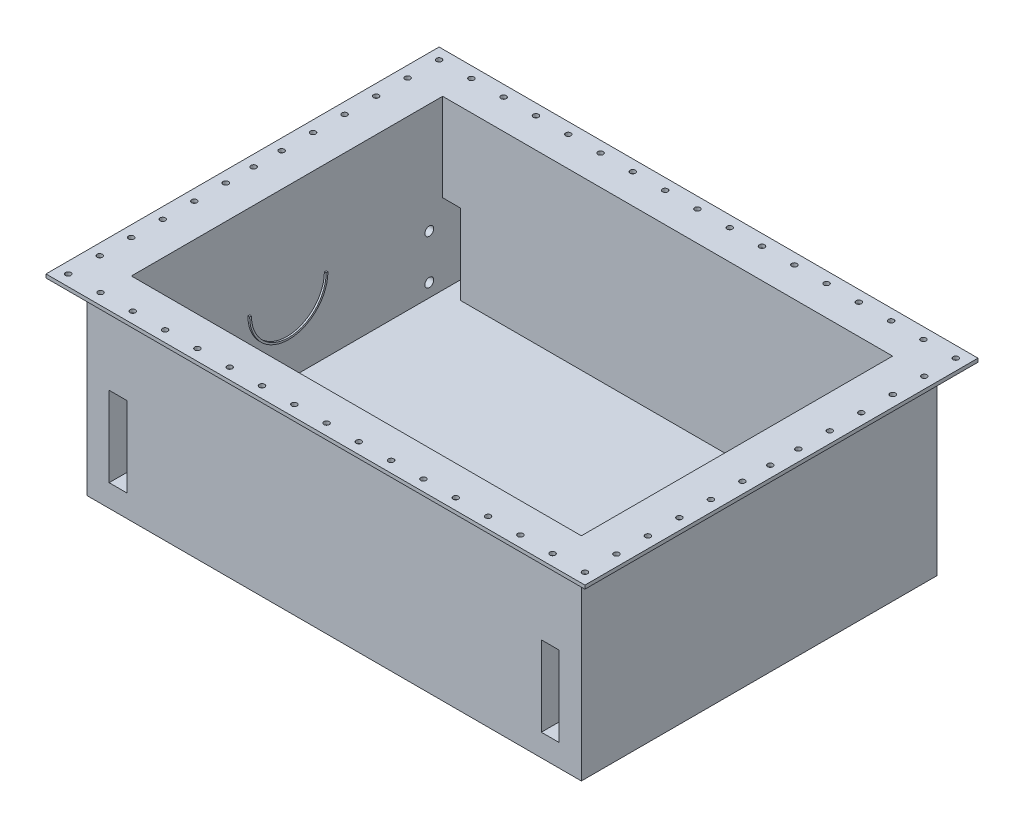
SolidWorks part; units mm, degrees
material "2195 Aluminum"
ref_plane "Front Plane" through (0, 0, 0) normal (0, 0, 1) x (1, 0, 0)
ref_plane "Top Plane" through (0, 0, 0) normal (0, 1, 0) x (1, 0, 0)
ref_plane "Right Plane" through (0, 0, 0) normal (1, 0, 0) x (0, 0, -1)
sketch "Sketch2" plane through (0, 0, 0) normal (0, 1, 0) x (1, 0, 0)
  line L0 (0, 437.5) -> (0, -437.5) construction
  line L1 (-632.5, 437.5) -> (632.5, 437.5)
  line L2 (-632.5, 437.5) -> (-632.5, -437.5)
  line L3 (-632.5, -437.5) -> (632.5, -437.5)
  line L4 (632.5, 437.5) -> (632.5, -437.5)
  line L5 (-632.5, 0) -> (632.5, 0) construction
  line L6 (-695, 48.7342) -> (-632.5, 48.7342) construction
  line L7 (-695, 500) -> (695, 500)
  line L8 (-695, 500) -> (-695, -500)
  line L9 (-695, -500) -> (695, -500)
  line L10 (695, 500) -> (695, -500)
  line L11 (632.5, 75.1796) -> (695, 75.1796) construction
  line L12 (-4.9015, 500) -> (-4.9015, 437.5) construction
  line L13 (-4.9015, -437.5) -> (-4.9015, -500) construction
  dimension "D1" = 62.5
  dimension "D2" = 1000
  dimension "D3" = 1390
extrude "Boss-Extrude1" add sketch "Sketch2" against normal blind 534.5
sketch "Sketch3" plane through (0, -534.5, 0) normal (0, -1, 0) x (1, 0, 0)
  line L0 (-695, 500) -> (-695, -500)
  line L3 (-695, 500) -> (695, 500)
  line L4 (695, -500) -> (695, 500)
  line L5 (-695, -500) -> (695, -500)
  line L6 (695, 500) -> (695, -500) construction
  line L7 (-695, 500) -> (695, 500) construction
  line L8 (-695, -500) -> (-695, 500) construction
  line L9 (695, -500) -> (-695, -500) construction
extrude "Boss-Extrude2" add sketch "Sketch3" against normal blind 62.5
sketch "Sketch4" plane through (695, 0, 0) normal (1, 0, 0) x (0, 0, -1)
  line L1 (0, 0) -> (0, -580.2055) construction
  line L2 (-105, -261) -> (-110, -261)
  line L3 (105, -261) -> (110, -261)
  arc A0 (-105, -261) -> (105, -261) centre (0, -261) ccw
  arc A1 (-110, -261) -> (110, -261) centre (0, -261) ccw
  dimension "D2" = 210
  dimension "D3" = 220
  dimension "D1" = 261
extrude "MMRTG Holder" add sketch "Sketch4" against normal blind 5 from offset 62.5 offset against normal yes
mirror "Mirror1" about plane through (0, 0, 0) normal (1, 0, 0) of "MMRTG Holder"
sketch "Sketch5" plane through (695, 0, 0) normal (1, 0, 0) x (0, 0, -1)
  line L0 (0, 70.8163) -> (0, -598.8061) construction
  line L1 (-500, -534.5) -> (500, -534.5) construction
  line L2 (-500, -534.5) -> (-500, 0) construction
  line L3 (-400, 39.1953) -> (-400, -618.3368) construction
  circle A0 centre (-400, -309.5) radius 12.5
  circle A1 centre (-400, -434.5) radius 12.5
  circle A2 centre (400, -434.5) radius 12.5
  circle A3 centre (400, -309.5) radius 12.5
  dimension "D4" = 25
  dimension "D1" = 125
  dimension "D2" = 100
  dimension "D3" = 100
extrude "Suspension Bolt Holes" cut sketch "Sketch5" against normal through all
sketch "Sketch6" plane through (0, 0, -500) normal (0, 0, -1) x (-1, 0, 0)
  line L0 (-695, -534.5) -> (-695, 0) construction
  line L1 (-632.5, -472) -> (-582.5, -472)
  line L2 (-632.5, -472) -> (-632.5, -247)
  line L3 (-632.5, -247) -> (-582.5, -247)
  line L4 (-582.5, -472) -> (-582.5, -247)
  line L5 (-695, -534.5) -> (695, -534.5) construction
  dimension "D1" = 62.5
  dimension "D2" = 62.5
  dimension "D3" = 50
  dimension "D4" = 225
extrude "Control Arm Cutout" cut sketch "Sketch6" against normal up to next
mirror "Mirror2" about plane through (0, 0, 0) normal (1, 0, 0) of "Control Arm Cutout"
mirror "Mirror3" about plane through (0, 0, 0) normal (0, 0, 1) of "Mirror2", "Control Arm Cutout"
sketch "Sketch7" plane through (0, 0, 0) normal (0, 1, 0) x (1, 0, 0)
  line L0 (695, 500) -> (-695, 500) construction
  line L1 (-757.5, 552.5) -> (757.5, 552.5)
  line L2 (-757.5, 552.5) -> (-757.5, -552.5)
  line L3 (-757.5, -552.5) -> (757.5, -552.5)
  line L4 (757.5, 552.5) -> (757.5, -552.5)
  line L5 (695, -500) -> (695, 500) construction
  line L7 (0, 552.5) -> (0, 500) construction
  line L8 (-632.5, 437.5) -> (632.5, 437.5)
  line L10 (0, -552.5) -> (0, -500) construction
  line L11 (-695, -500) -> (695, -500) construction
  line L12 (-632.5, 437.5) -> (-632.5, -437.5)
  line L13 (-632.5, -437.5) -> (632.5, -437.5)
  line L14 (632.5, 437.5) -> (632.5, -437.5)
  dimension "D1" = 52.5
  dimension "D2" = 62.5
  dimension "D3" = 52.5
extrude "AttachRoverFlange" add sketch "Sketch7" against normal blind 10
sketch "Sketch10" plane through (0, 0, 0) normal (0, 1, 0) x (1, 0, 0)
  line L0 (-726.25, 521.25) -> (-726.25, -475.2943) construction
  line L1 (-757.5, 552.5) -> (-757.5, -552.5) construction
  line L2 (757.5, 552.5) -> (-757.5, 552.5) construction
  line L3 (0, 0) -> (-1003.0581, 0) construction
  line L4 (-733.75, 0) -> (-718.75, 0)
  line L5 (0, 0) -> (0, 752.0536) construction
  line L6 (-726.25, 521.25) -> (0, 521.25) construction
  line L7 (0, 538.75) -> (0, 523.75)
  circle A0 centre (-726.25, 521.25) radius 7.5
  circle A1 centre (-726.25, 432.7083) radius 7.5
  circle A2 centre (-726.25, 344.1667) radius 7.5
  circle A3 centre (-726.25, 255.625) radius 7.5
  circle A4 centre (-635.4688, 521.25) radius 7.5
  circle A5 centre (-726.25, 167.0833) radius 7.5
  circle A6 centre (-726.25, 78.5417) radius 7.5
  circle A7 centre (-726.25, 0) radius 7.5
  circle A8 centre (-544.6875, 521.25) radius 7.5
  circle A9 centre (-453.9062, 521.25) radius 7.5
  circle A10 centre (-363.125, 521.25) radius 7.5
  circle A11 centre (-272.3438, 521.25) radius 7.5
  circle A12 centre (-181.5625, 521.25) radius 7.5
  circle A13 centre (0, 521.25) radius 7.5
  circle A14 centre (-90.7813, 521.25) radius 7.5
  circle A15 centre (90.7813, 521.25) radius 7.5
  circle A16 centre (181.5625, 521.25) radius 7.5
  circle A17 centre (272.3438, 521.25) radius 7.5
  circle A18 centre (363.125, 521.25) radius 7.5
  circle A19 centre (453.9062, 521.25) radius 7.5
  circle A20 centre (544.6875, 521.25) radius 7.5
  circle A21 centre (635.4688, 521.25) radius 7.5
  circle A22 centre (726.25, 521.25) radius 7.5
  circle A23 centre (726.25, 0) radius 7.5
  circle A24 centre (726.25, 78.5417) radius 7.5
  circle A25 centre (726.25, 167.0833) radius 7.5
  circle A26 centre (726.25, 255.625) radius 7.5
  circle A27 centre (726.25, 344.1667) radius 7.5
  circle A28 centre (726.25, 432.7083) radius 7.5
  circle A29 centre (726.25, -78.5417) radius 7.5
  circle A30 centre (726.25, -167.0833) radius 7.5
  circle A31 centre (726.25, -255.625) radius 7.5
  circle A32 centre (726.25, -344.1667) radius 7.5
  circle A33 centre (726.25, -432.7083) radius 7.5
  circle A34 centre (726.25, -521.25) radius 7.5
  circle A35 centre (635.4688, -521.25) radius 7.5
  circle A36 centre (544.6875, -521.25) radius 7.5
  circle A37 centre (453.9063, -521.25) radius 7.5
  circle A38 centre (363.125, -521.25) radius 7.5
  circle A39 centre (272.3438, -521.25) radius 7.5
  circle A40 centre (181.5625, -521.25) radius 7.5
  circle A41 centre (90.7813, -521.25) radius 7.5
  circle A42 centre (0, -521.25) radius 7.5
  circle A43 centre (-90.7812, -521.25) radius 7.5
  circle A44 centre (-181.5625, -521.25) radius 7.5
  circle A45 centre (-272.3437, -521.25) radius 7.5
  circle A46 centre (-363.125, -521.25) radius 7.5
  circle A47 centre (-453.9062, -521.25) radius 7.5
  circle A48 centre (-544.6875, -521.25) radius 7.5
  circle A49 centre (-635.4687, -521.25) radius 7.5
  circle A50 centre (-726.25, -521.25) radius 7.5
  circle A51 centre (-726.25, -344.1667) radius 7.5
  circle A52 centre (-726.25, -432.7083) radius 7.5
  circle A53 centre (-726.25, -255.625) radius 7.5
  circle A54 centre (-726.25, -167.0833) radius 7.5
  circle A55 centre (-726.25, -78.5417) radius 7.5
  dimension "D1" = 15
  dimension "D2" = 31.25
  dimension "D3" = 31.25
  dimension "D4" = 88.5417
  dimension "D5" = 88.5417
  dimension "D6" = 88.5417
  dimension "D7" = 88.5417
  dimension "D8" = 88.5417
  dimension "D9" = 90.7812
  dimension "D10" = 90.7812
  dimension "D11" = 90.7812
  dimension "D12" = 90.7812
  dimension "D13" = 90.7812
  dimension "D14" = 90.7812
  dimension "D15" = 90.7812
extrude "Attachment Holes" cut sketch "Sketch10" against normal up to next (10 mm away) contours L4 A7 | L4 A7 | A6 | A5 | A3 | A2 | A1 | A0 | A4 | A8 | A9 | A10 | A11 | A12 | A14 | L7 A13 | L7 A13 | A15 | A16 | A17 | A18 | A19 | A20 | A21 | A22 | A28 | A27 | A26 | A25 | A24 | A23 | A29 | A30 | A31 | A32 | A33 | A34 | A35 | A36 | A39 | A38 | A37 | A42 | A41 | A40 | A43 | A44 | A45 | A46 | A47 | A48 | A49 | A50 | A52 | A51 | A55 | A54 | A53 region at (-726.25, 0, -3.1831) region at (-726.25, 0, 3.1831) region at (-726.25, 0, -521.25) region at (-726.25, 0, -432.7083) region at (-726.25, 0, -344.1667) region at (-726.25, 0, -255.625) region at (-635.4688, 0, -521.25) region at (-726.25, 0, -167.0833) region at (-726.25, 0, -78.5417) region at (-544.6875, 0, -521.25) region at (-453.9062, 0, -521.25) region at (-363.125, 0, -521.25) region at (-272.3438, 0, -521.25) region at (-181.5625, 0, -521.25) region at (0, 0, -521.25) region at (-90.7813, 0, -521.25) region at (90.7813, 0, -521.25) region at (181.5625, 0, -521.25) region at (272.3438, 0, -521.25) region at (363.125, 0, -521.25) region at (453.9062, 0, -521.25) region at (544.6875, 0, -521.25) region at (635.4688, 0, -521.25) region at (726.25, 0, -521.25) region at (726.25, 0, 0) region at (726.25, 0, -78.5417) region at (726.25, 0, -167.0833) region at (726.25, 0, -255.625) region at (726.25, 0, -344.1667) region at (726.25, 0, -432.7083) region at (726.25, 0, 78.5417) region at (726.25, 0, 167.0833) region at (726.25, 0, 255.625) region at (726.25, 0, 344.1667) region at (726.25, 0, 432.7083) region at (726.25, 0, 521.25) region at (635.4688, 0, 521.25) region at (544.6875, 0, 521.25) region at (453.9063, 0, 521.25) region at (363.125, 0, 521.25) region at (272.3438, 0, 521.25) region at (181.5625, 0, 521.25) region at (90.7813, 0, 521.25) region at (0, 0, 521.25) region at (-90.7812, 0, 521.25) region at (-181.5625, 0, 521.25) region at (-272.3437, 0, 521.25) region at (-363.125, 0, 521.25) region at (-453.9062, 0, 521.25) region at (-544.6875, 0, 521.25) region at (-635.4687, 0, 521.25) region at (-726.25, 0, 521.25) region at (-726.25, 0, 344.1667) region at (-726.25, 0, 432.7083) region at (-726.25, 0, 255.625) region at (-726.25, 0, 167.0833) region at (-726.25, 0, 78.5417)
sketch "Sketch11" plane through (695, 0, 0) normal (1, 0, 0) x (0, 0, -1)
  circle A0 centre (-400, -309.5) radius 12.5
  circle A1 centre (-400, -434.5) radius 12.5
  circle A2 centre (400, -309.5) radius 12.5
  circle A3 centre (400, -434.5) radius 12.5
  circle A4 centre (400, -309.5) radius 12.5 construction
  circle A5 centre (400, -434.5) radius 12.5 construction
  circle A6 centre (-400, -309.5) radius 12.5 construction
  circle A7 centre (-400, -434.5) radius 12.5 construction
extrude "Boss-Extrude3" add sketch "Sketch11" against normal blind 5
mirror "Mirror4" about plane through (0, 0, 0) normal (1, 0, 0) of "Boss-Extrude3"
equation "\"D3@Sketch2\"=1140+(4*(62.5))"
equation "\"D1@Boss-Extrude1\"=422+62.5+50"
equation "\"D4@Sketch10\"=531.25/6"
equation "\"D5@Sketch10\"=531.25/6"
equation "\"D6@Sketch10\"=531.25/6"
equation "\"D7@Sketch10\"=531.25/6"
equation "\"D8@Sketch10\"=531.25/6"
equation "\"D9@Sketch10\"=726.25/8"
equation "\"D10@Sketch10\"=726.25/8"
equation "\"D11@Sketch10\"=726.25/8"
equation "\"D12@Sketch10\"=726.25/8"
equation "\"D13@Sketch10\"=726.25/8"
equation "\"D14@Sketch10\"=726.25/8"
equation "\"D15@Sketch10\"=726.25/8"
